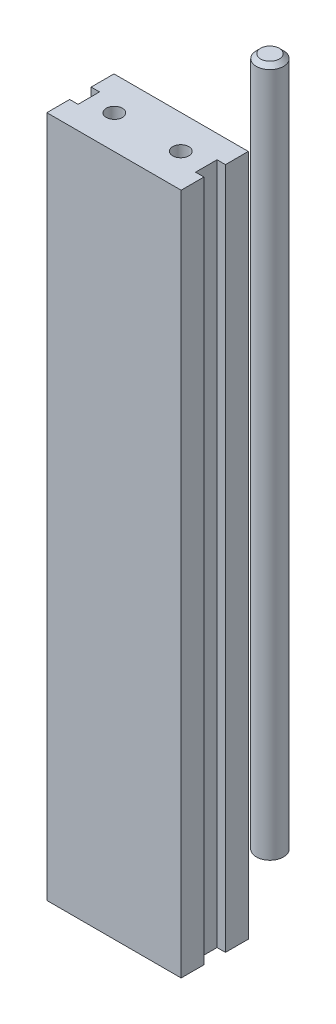
SolidWorks part; units mm, degrees
ref_plane "Front Plane" through (0, 0, 0) normal (0, 0, 1) x (1, 0, 0)
ref_plane "Top Plane" through (0, 0, 0) normal (0, 1, 0) x (1, 0, 0)
ref_plane "Right Plane" through (0, 0, 0) normal (1, 0, 0) x (0, 0, -1)
sketch "Sketch1" plane through (0, 0, 0) normal (0, 1, 0) x (1, 0, 0)
  line L0 (-20, 10) -> (20, -10) construction
  line L1 (-20, 10) -> (20, 10)
  line L2 (-20, 10) -> (-20, -10)
  line L3 (-20, -10) -> (20, -10)
  line L4 (20, 10) -> (20, -10)
  dimension "D1" = 40
  dimension "D2" = 20
extrude "Boss-Extrude1" add sketch "Sketch1" along normal mid plane 203.2
sketch "Sketch2" plane through (0, 101.6, 0) normal (0, 1, 0) x (1, 0, 0)
  line L0 (-20, 10) -> (-20, -10) construction
  line L1 (-20, 3.2) -> (-17.5, 3.2)
  line L2 (-20, 3.2) -> (-20, -3.2)
  line L3 (-20, -3.2) -> (-17.5, -3.2)
  line L4 (-17.5, 3.2) -> (-17.5, -3.2)
  line L5 (0, 10) -> (0, -10) construction
  line L6 (20, 10) -> (-20, 10) construction
  line L7 (-20, -10) -> (20, -10) construction
  line L8 (17.5, 3.2) -> (17.5, -3.2)
  line L9 (20, -3.2) -> (17.5, -3.2)
  line L10 (20, 3.2) -> (20, -3.2)
  line L11 (20, 3.2) -> (17.5, 3.2)
  point P16 (-20, 0)
  point P17 (0, 0)
  dimension "D1" = 6.4
  dimension "D2" = 2.5
extrude "Cut-Extrude1" cut sketch "Sketch2" against normal through all
sketch "Sketch3" plane through (0, 101.6, 0) normal (0, 1, 0) x (1, 0, 0)
  line L0 (-9.9, 0) -> (9.9, 0) construction
  circle A0 centre (-9.9, 0) radius 2.4
  circle A1 centre (9.9, 0) radius 2.4
  dimension "D1" = 4.8
  dimension "D2" = 19.8
extrude "Cut-Extrude2" cut sketch "Sketch3" against normal through all
sketch "Sketch4" plane through (0, 101.6, 0) normal (0, 1, 0) x (1, 0, 0)
  line L0 (0, 36.45) -> (0, 0) construction
  line L1 (20, 10) -> (-20, 10) construction
  circle A0 centre (0, 36.45) radius 4.05
  point P2 (0, 32.4)
  dimension "D2" = 8.1
  dimension "D1" = 22.4
extrude "Boss-Extrude2" add sketch "Sketch4" against normal up to surface (203.2 mm away) and the other way blind 2 separate body up to face at (-9.9, -101.6, 2.4)
chamfer "Chamfer1" distance 1.27 angle 45 1 edges at (0, 103.6, -32.4)
